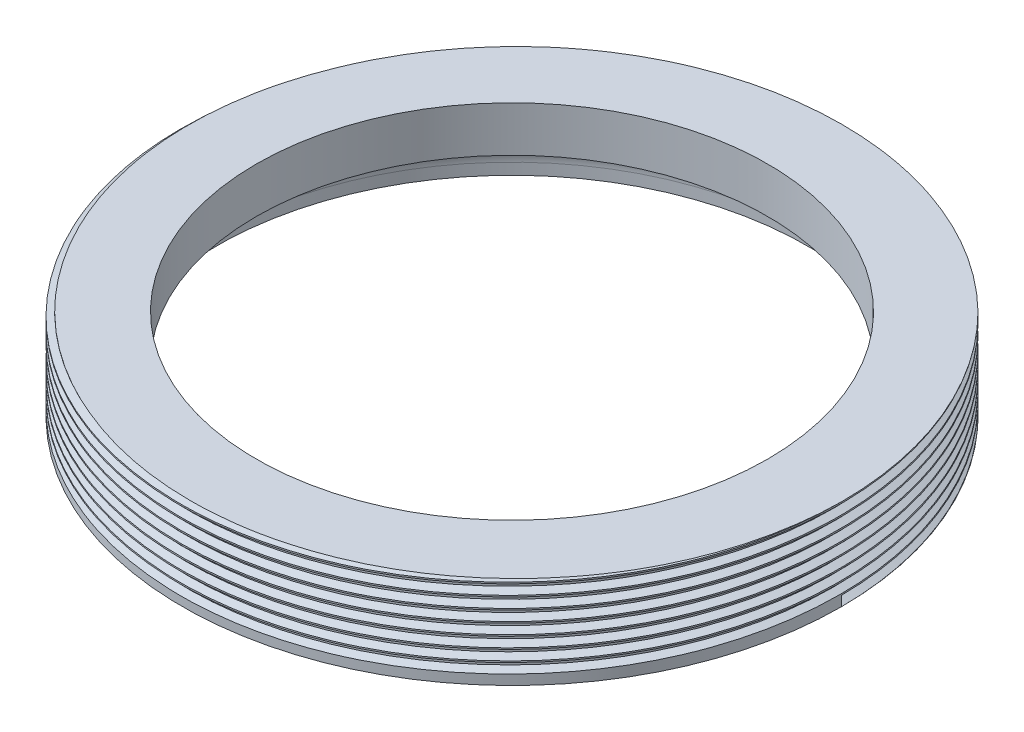
SolidWorks part; units mm, degrees
ref_plane "Front Plane" through (0, 0, 0) normal (0, 0, 1) x (1, 0, 0)
ref_plane "Top Plane" through (0, 0, 0) normal (0, 1, 0) x (1, 0, 0)
ref_plane "Right Plane" through (0, 0, 0) normal (1, 0, 0) x (0, 0, -1)
ref_axis "Axis1" through (0, 10.5, 0) along (0, -1, 0)
sketch "Sketch2" plane through (0, 0, 0) normal (0, 0, -1) x (-1, 0, 0)
  line L0 (0, 0) -> (0, 6.9818) construction
  line L1 (0, 0) -> (26, 0) construction
  line L4 (22.5, 4) -> (22.5, 8)
  line L5 (22.5, 8) -> (29, 8)
  line L6 (29, 8) -> (29, 0)
  line L7 (29, 0) -> (26, 0)
  line L8 (22.5, 4) -> (26, 4) construction
  line L9 (26, 4) -> (26, 0) construction
  line L10 (22.5, 4) -> (23, 4)
  line L11 (26, 0) -> (26, 1)
  arc A0 (23, 4) -> (26, 1) centre (23, 1) cw
  point P12 (26, 1.259)
  point P13 (0, 0)
  dimension "D1" = 4
  dimension "D2" = 8
  dimension "D3" = 29
  dimension "D4" = 26
  dimension "D5" = 3.5
  dimension "D6" = 0.5
revolve "Revolve1" add sketch "Sketch2" angle 360 about L0
thread "Thread1" pitch 1 method cut profile "Thread Profile1" start angle 0, offset 0, length 0, pitch 1, diameter 58
ref_plane "Plane1" through (29, 0, 0) normal (0, 0, 1) x (1, 0, 0)
sketch "Thread Profile1" plane through (29, 0, 0) normal (0, 0, 1) x (1, 0, 0)
  line L0 (0, 0) -> (0, 1) construction
  line L11 (0, 0) -> (0, 0.875)
  line L12 (0, 0.875) -> (-0.5413, 0.5625)
  line L13 (-0.5413, 0.5625) -> (-0.5413, 0.3125)
  line L15 (-0.5413, 0.3125) -> (0, 0)
  line L17 (-0.5413, 0.4375) -> (0, 0.4375) construction
  point P2 (0, 0)
  dimension "Pitch" = 1
  dimension "Profile_Angle" = 60
  dimension "Profile_Land" = 0.25
  dimension "Profile_Height" = 0.5413
